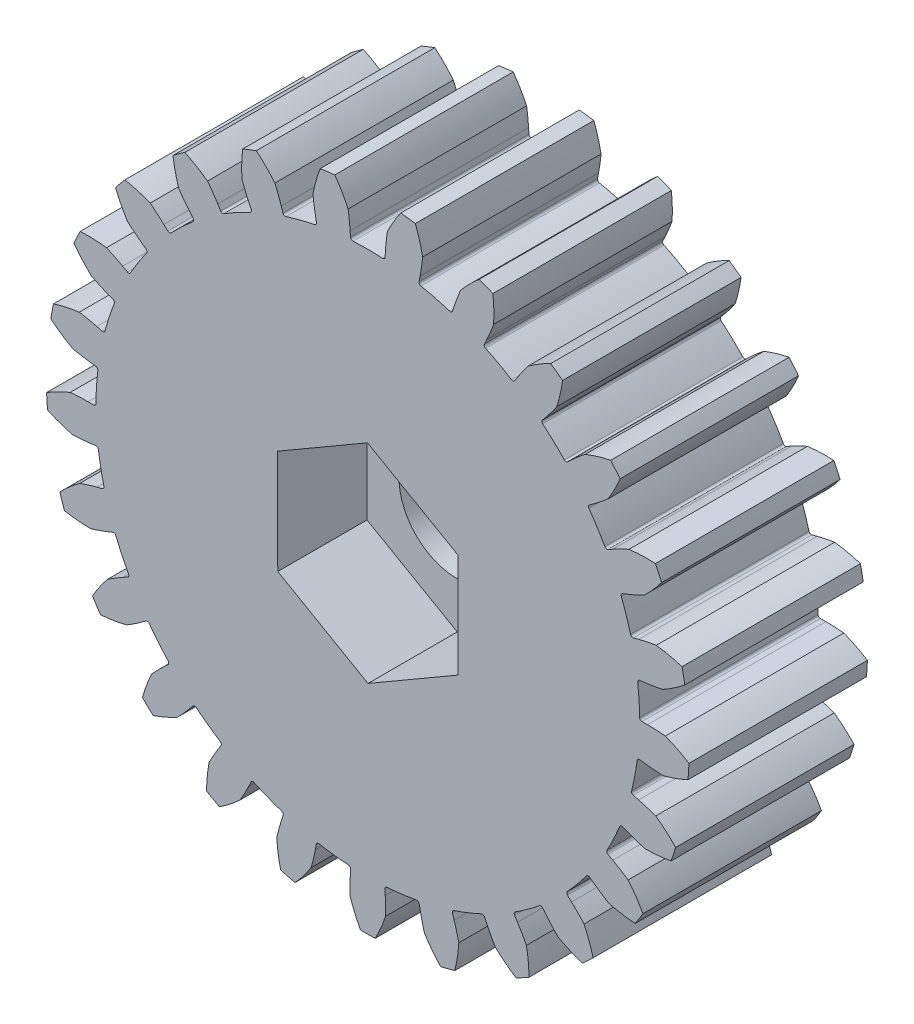
SolidWorks part; units mm, degrees
ref_plane "Plano frontal" through (0, 0, 0) normal (0, 0, 1) x (1, 0, 0)
ref_plane "Plano superior" through (0, 0, 0) normal (0, 1, 0) x (1, 0, 0)
ref_plane "Plano direito" through (0, 0, 0) normal (1, 0, 0) x (0, 0, -1)
sketch "Esboço1" plane through (0, 0, -10.2037) normal (0, 0, 1) x (1, 0, 0)
  circle A0 centre (175.26, 0) radius 7.14
  circle A1 centre (175.26, 0) radius 18.009
  circle A3 centre (175.26, 0) radius 7.14 construction
  circle A6 centre (175.26, 0) radius 7.14 construction
  dimension "D1" = 36.018
extrude "Ressalto-extrusão1" add sketch "Esboço1" against normal up to surface (5 mm away) contours A0
extrude "Ressalto-extrusão2" add sketch "Esboço1<3>" along normal up to surface (10 mm away) contours A1
sketch "Esboço1<3>" plane through (0, 0, -10.2037) normal (0, 0, 1) x (1, 0, 0) same geometry as "Esboço1"
sketch "Esboço2" plane through (0, 0, -0.2037) normal (0, 0, 1) x (1, 0, 0)
  circle A0 centre (175.26, 0) radius 3.25
  dimension "D1" = 6.5
extrude "Corte-extrusão1" cut sketch "Esboço2" against normal through all
sketch "Esboço3" plane through (0, 0, -0.2037) normal (0, 0, 1) x (1, 0, 0)
  line L0 (175.26, 0) -> (175.26, 18.009) construction
  line L2 (176.2304, 15.3293) -> (176.25, 15.6382)
  line L4 (174.27, 15.6382) -> (174.2896, 15.3293)
  circle A0 centre (175.26, 0) radius 15.2305 construction
  circle A1 centre (175.26, 0) radius 15.6695 construction
  circle A2 centre (175.26, 0) radius 16.675 construction
  circle A3 centre (175.26, 0) radius 18.009 construction
  arc A4 (174.27, 15.6382) -> (174.16, 16.6387) centre (163.4148, 14.951) ccw
  arc A5 (174.16, 16.6387) -> (173.4126, 17.914) centre (166.6756, 13.1088) ccw
  arc A6 (176.25, 15.6382) -> (176.36, 16.6387) centre (187.1052, 14.951) cw
  arc A7 (176.36, 16.6387) -> (177.1074, 17.914) centre (183.8444, 13.1088) cw
  arc A8 (174.4264, 15.2077) -> (176.0936, 15.2077) centre (175.26, 0) cw
  arc A10 (174.4264, 15.2077) -> (174.2896, 15.3293) centre (174.4193, 15.3375) cw
  arc A11 (176.0936, 15.2077) -> (176.2304, 15.3293) centre (176.1007, 15.3375) ccw
  arc A12 (173.4126, 17.914) -> (177.1074, 17.914) centre (175.26, 0) cw
  point P38 (174.2977, 15.2001)
  point P41 (176.2223, 15.2001)
  dimension "D1" = 30.461
  dimension "D2" = 33.35
  dimension "D3" = 31.339
  dimension "D5" = 1.98
  dimension "D6" = 0.13
  dimension "D7" = 8.275
  dimension "D4" = 2.2
extrude "Corte-extrusão2" cut sketch "Esboço3" against normal blind 10
pattern_circular "PadrãoCircular1" count 25 over 360 about axis through (175.26, 0, -0.2037) along (0, 0, -1) of "Corte-extrusão2"
sketch "Esboço4" plane through (0, 0, -0.2037) normal (0, 0, 1) x (1, 0, 0)
  line L1 (175.2467, 5.8312) -> (170.2034, 2.9041)
  line L2 (170.2034, 2.9041) -> (170.2167, -2.9271)
  line L3 (170.2167, -2.9271) -> (175.2733, -5.8312)
  line L4 (175.2733, -5.8312) -> (180.3166, -2.9041)
  line L5 (180.3166, -2.9041) -> (180.3033, 2.9271)
  line L6 (180.3033, 2.9271) -> (175.2467, 5.8312)
  circle A0 centre (175.26, 0) radius 5.05 construction
  dimension "D1" = 10.1
extrude "Corte-extrusão3" cut sketch "Esboço4" against normal blind 5
